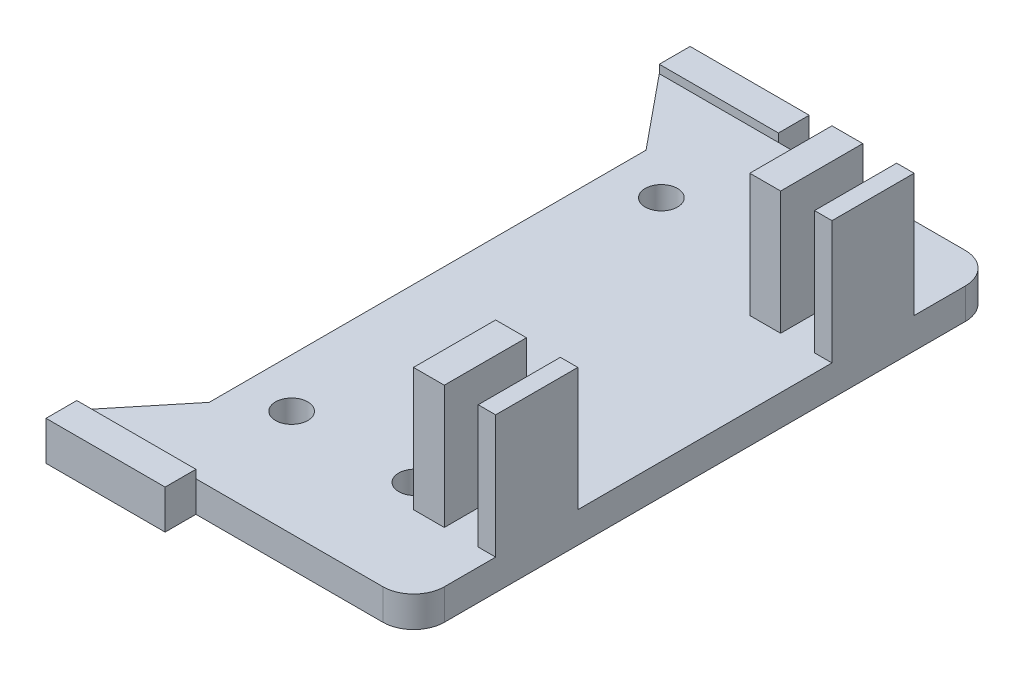
SolidWorks part; units mm, degrees
ref_plane "Front Plane" through (0, 0, 0) normal (0, 0, 1) x (1, 0, 0)
ref_plane "Top Plane" through (0, 0, 0) normal (0, 1, 0) x (1, 0, 0)
ref_plane "Right Plane" through (0, 0, 0) normal (1, 0, 0) x (0, 0, -1)
sketch "Sketch1" plane through (0, 0, 0) normal (0, 1, 0) x (1, 0, 0)
  line L0 (-19.3, -28.36) -> (-13.5, -21.27)
  line L1 (-13.5, 28.36) -> (13.5, 28.36)
  line L2 (-13.5, 28.36) -> (-13.5, -28.36)
  line L3 (-13.5, -28.36) -> (13.5, -28.36)
  line L4 (13.5, 28.36) -> (13.5, -28.36)
  line L5 (-13.5, 28.36) -> (13.5, -28.36) construction
  line L6 (-13.5, -28.36) -> (13.5, 28.36) construction
  line L7 (-19.3, 28.36) -> (-13.5, 21.27)
  line L8 (-19.3, -28.36) -> (-13.5, -28.36)
  line L9 (-7.7, -31.36) -> (-7.7, -28.36)
  line L10 (-28.9735, 0) -> (22.876, 0)
  line L11 (-19.3, -31.36) -> (-7.7, -31.36)
  line L12 (-19.3, -31.36) -> (-19.3, -28.36)
  line L13 (8.5, 20.375) -> (11.8, 20.375)
  line L14 (13.5, -1.0223) -> (8.5, -1.0223)
  line L15 (8.5, 12.375) -> (8.5, -12.375)
  line L16 (8.5, -12.375) -> (8.5, -20.375)
  line L17 (8.5, 12.375) -> (5.5, 12.375)
  line L18 (8.5, 12.375) -> (8.5, 20.375)
  line L19 (8.5, 20.375) -> (5.5, 20.375)
  line L20 (5.5, 12.375) -> (5.5, 20.375)
  line L21 (8.5, -12.375) -> (5.5, -12.375)
  line L22 (8.5, -20.375) -> (5.5, -20.375)
  line L23 (5.5, -12.375) -> (5.5, -20.375)
  line L24 (3.2616, -18) -> (3.2616, 18)
  line L25 (3.2616, -8.5923) -> (-2.7384, -8.5923)
  line L26 (-2.7384, -13.232) -> (-2.7384, 19.6093)
  line L27 (-8.7384, -18) -> (-8.7384, 18)
  line L28 (-19.3, 31.36) -> (-7.7, 31.36)
  line L29 (-7.7, 31.36) -> (-7.7, 28.36)
  line L30 (-19.3, 31.36) -> (-19.3, 28.36)
  line L31 (-19.3, 28.36) -> (-13.5, 28.36)
  line L32 (-13.5, 28.36) -> (-13.5, 31.36)
  line L33 (11.8, -12.375) -> (13.5, -12.375)
  line L34 (11.8, 20.375) -> (13.5, 20.375)
  line L35 (11.8, 20.375) -> (11.8, 12.375)
  line L36 (11.8, 12.375) -> (13.5, 12.375)
  line L37 (13.5, 20.375) -> (13.5, 12.375)
  line L38 (13.5, -20.375) -> (13.5, -12.375)
  line L39 (11.8, -20.375) -> (13.5, -20.375)
  line L40 (11.8, -20.375) -> (11.8, -12.375)
  circle A0 centre (3.2616, 18) radius 1.575
  circle A3 centre (3.2616, -18) radius 1.575
  circle A4 centre (-8.7384, -18) radius 1.575
  circle A5 centre (-8.7384, 18) radius 1.575
  point P0 (0, 0)
  point P23 (8.5, 0)
  point P42 (-3.2616, 0)
  point P43 (3.2616, 0)
  dimension "D10" = 3.15
  dimension "D1" = 56.72
  dimension "D2" = 27
  dimension "D3" = 3
  dimension "D4" = 3.3
  dimension "D5" = 5
  dimension "D6" = 24.75
  dimension "D7" = 3
  dimension "D8" = 8
  dimension "D9" = 18
  dimension "D11" = 6
  dimension "D12" = 11.6
extrude "Boss-Extrude1" add sketch "Sketch1" along normal blind 3 contours L17 L20 L19 L18 L14 L4 L1 L2 L10 L15 | L23 L21 L10 L2 L3 L4 L16 L22 | L26 L25 L24 L10 | L0 L8 L2 | L31 L7 L2 | L36 L35 L13 L18 L15 L10 L4 | L10 L15 L14 L4 region at (-15.4333, 0, 25.9967) region at (-0.5597, 0, 14.8468) region at (-1.9959, 0, -14.6518) region at (-15.4333, 0, -25.9967) region at (0.2616, 0, 4.2962) region at (10.7458, 0, -9.2342) region at (11, 0, 0.5112)
extrude "Boss-Extrude2" add sketch "Sketch1<3>" along normal blind 15 contours L20 L17 L18 L19 | L21 L23 L22 L16 | L40 L33 L38 L39 | L35 L36 L37 L34 region at (7, 0, 16.375) region at (7, 0, -16.375)
sketch "Sketch1<3>" plane through (0, 0, 0) normal (0, 1, 0) x (1, 0, 0) same geometry as "Sketch1"
sketch "Sketch2" plane through (0, 0, 0) normal (1, 0, 0) x (0, 0, -1)
  line L0 (14.25, 3) -> (-14.25, 3)
  line L3 (28.36, 3) -> (20.375, 3) construction
  line L4 (-12.375, 3) -> (-20.375, 3) construction
  line L5 (-14.25, 3) -> (-14.25, 8.75)
  line L6 (0, 16.9422) -> (0, -6.1776)
  line L7 (14.25, 3) -> (14.25, 8.75)
  circle A0 centre (-14.25, 8.75) radius 1.05
  circle A1 centre (14.25, 8.75) radius 1.05
  point P12 (0, 3)
  dimension "D3" = 2.1
  dimension "D1" = 14.25
  dimension "D2" = 5.75
extrude "Boss-Extrude3" add sketch "Sketch1<4>" along normal blind 3.8 contours L1 | L1 | L3 | L31 L32 L28 L30 region at (-13.5, 0, 29.86) region at (-10.6, 0, -29.86) region at (-16.4, 0, -29.86)
sketch "Sketch1<4>" plane through (0, 0, 0) normal (0, 1, 0) x (1, 0, 0) same geometry as "Sketch1"
fillet "Fillet1" radius 3 2 edges at (13.5, 1.5, -28.36) (13.5, 1.5, 28.36)
